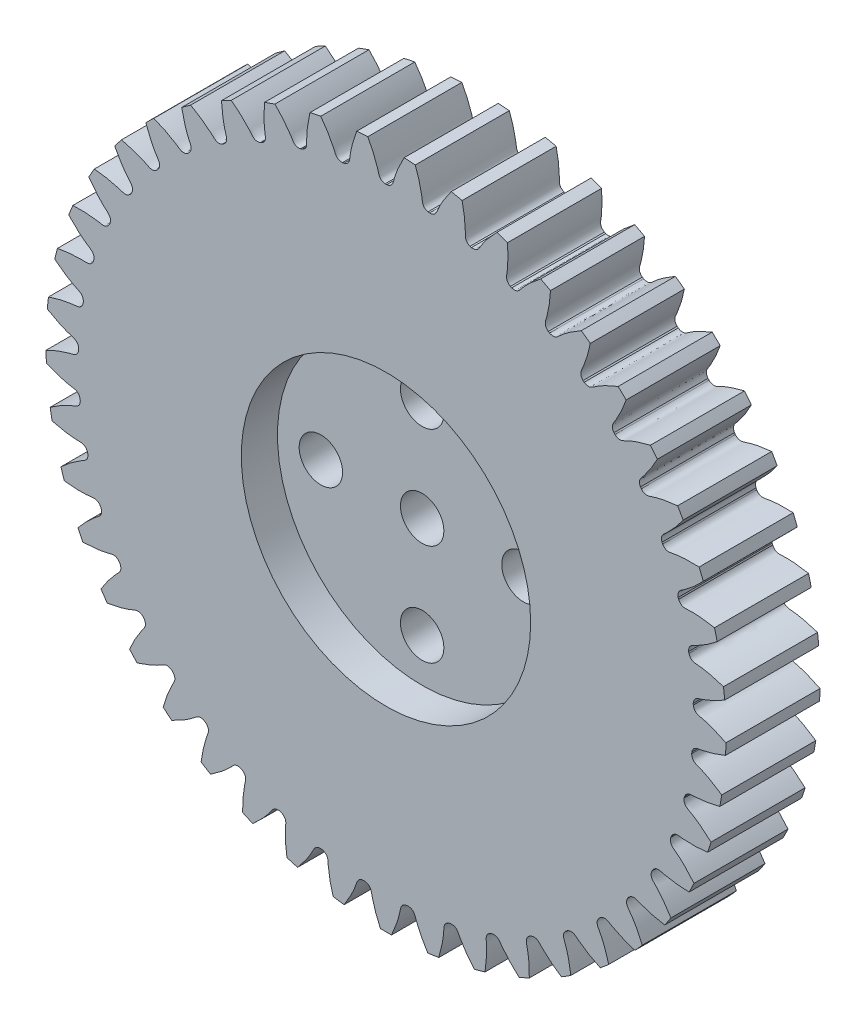
SolidWorks part; units mm, degrees
ref_plane "前视基准面" through (0, 0, 0) normal (0, 0, 1) x (1, 0, 0)
ref_plane "上视基准面" through (0, 0, 0) normal (0, 1, 0) x (1, 0, 0)
ref_plane "右视基准面" through (0, 0, 0) normal (1, 0, 0) x (0, 0, -1)
other "Configuration Table"
sketch "草图1" plane through (0, 0, 0) normal (0, 0, 1) x (1, 0, 0)
  circle A0 centre (0, 0) radius 23.5
extrude "凸台-拉伸1" add sketch "草图1" along normal blind 6.5
ref_axis "基准轴1" through (0, 0, 6.5) along (0, 0, -1)
sketch "草图2" plane through (0, 0, 0) normal (0, 0, 1) x (1, 0, 0)
  line L0 (0, 0) -> (0, 23.5) construction
  circle A0 centre (0, 0) radius 23.5 construction
  arc A1 (0.0519, 21.2499) -> (-0.0519, 21.2499) centre (0, 0) ccw
  arc A2 (3.8286, 26.7057) -> (-3.8286, 26.7057) centre (0, 0) ccw
  spline S0 degree 3 poles (0.0519, 21.2499) (0.4436, 21.3041) (0.4881, 21.5947) (0.5806, 21.9096) (0.6162, 22.0237) (0.6568, 22.145) (0.7027, 22.2735) (0.7541, 22.4089) (0.8114, 22.5512) (0.8748, 22.7) (0.9447, 22.8553) (1.0213, 23.0167) (1.1048, 23.1842) (1.1956, 23.3575) (1.294, 23.5363) (1.4001, 23.7204) (1.5142, 23.9097) (1.6367, 24.1037) (1.7676, 24.3024) (1.9073, 24.5053) (2.0559, 24.7123) (2.2137, 24.923) (2.3809, 25.1372) (2.5577, 25.3546) (2.7442, 25.5749) (2.9408, 25.7977) (3.1474, 26.0228) (3.4406, 26.3296) (3.6704, 26.5559) (3.8286, 26.7057) knots 0 0 0 0 0.112268 0.128789 0.146568 0.165606 0.185901 0.207456 0.230268 0.254339 0.279668 0.306255 0.334101 0.363205 0.393567 0.425188 0.458067 0.492204 0.527599 0.564253 0.602166 0.641336 0.681765 0.723452 0.766398 0.810601 0.856064 0.902784 1 1 1 1
  spline S1 degree 3 poles (-0.0519, 21.2499) (-0.4436, 21.3041) (-0.4881, 21.5947) (-0.5806, 21.9096) (-0.6162, 22.0237) (-0.6568, 22.145) (-0.7027, 22.2735) (-0.7541, 22.4089) (-0.8114, 22.5512) (-0.8748, 22.7) (-0.9447, 22.8553) (-1.0213, 23.0167) (-1.1048, 23.1842) (-1.1956, 23.3575) (-1.294, 23.5363) (-1.4001, 23.7204) (-1.5142, 23.9097) (-1.6367, 24.1037) (-1.7676, 24.3024) (-1.9073, 24.5053) (-2.0559, 24.7123) (-2.2137, 24.923) (-2.3809, 25.1372) (-2.5577, 25.3546) (-2.7442, 25.5749) (-2.9408, 25.7977) (-3.1474, 26.0228) (-3.4406, 26.3296) (-3.6704, 26.5559) (-3.8286, 26.7057) knots 0 0 0 0 0.112268 0.128789 0.146568 0.165606 0.185901 0.207456 0.230268 0.254339 0.279668 0.306255 0.334101 0.363205 0.393567 0.425188 0.458067 0.492204 0.527599 0.564253 0.602166 0.641336 0.681765 0.723452 0.766398 0.810601 0.856064 0.902784 1 1 1 1
extrude "切除-拉伸1" cut sketch "草图2" along normal through all
pattern_circular "阵列(圆周)1" count 45 every 8 about axis through (0, 0, 6.5) along (0, 0, -1) of "切除-拉伸1"
sketch "草图3" plane through (0, 0, 0) normal (0, 0, 1) x (1, 0, 0)
  circle A0 centre (0, 0) radius 22.5 construction
  dimension "Dn" = 45
sketch "草图4" plane through (0, 0, 6.5) normal (0, 0, 1) x (1, 0, 0)
  circle A0 centre (0, 0) radius 1.5
  dimension "D1" = 3
extrude "切除-拉伸2" cut sketch "草图4" against normal blind 10
sketch "草图5" plane through (0, 0, 6.5) normal (0, 0, 1) x (1, 0, 0)
  circle A0 centre (0, 0) radius 7 construction
  circle A1 centre (0, 7) radius 1.5
  circle A2 centre (7, 0) radius 1.5
  circle A3 centre (0, -7) radius 1.5
  circle A4 centre (-7, 0) radius 1.5
  dimension "D1" = 14
  dimension "D2" = 3
extrude "切除-拉伸3" cut sketch "草图5" against normal blind 10
sketch "草图6" plane through (0, 0, 6.5) normal (0, 0, 1) x (1, 0, 0)
  circle A0 centre (0, 0) radius 10
  dimension "D1" = 20
extrude "切除-拉伸4" cut sketch "草图6" against normal blind 2.5
